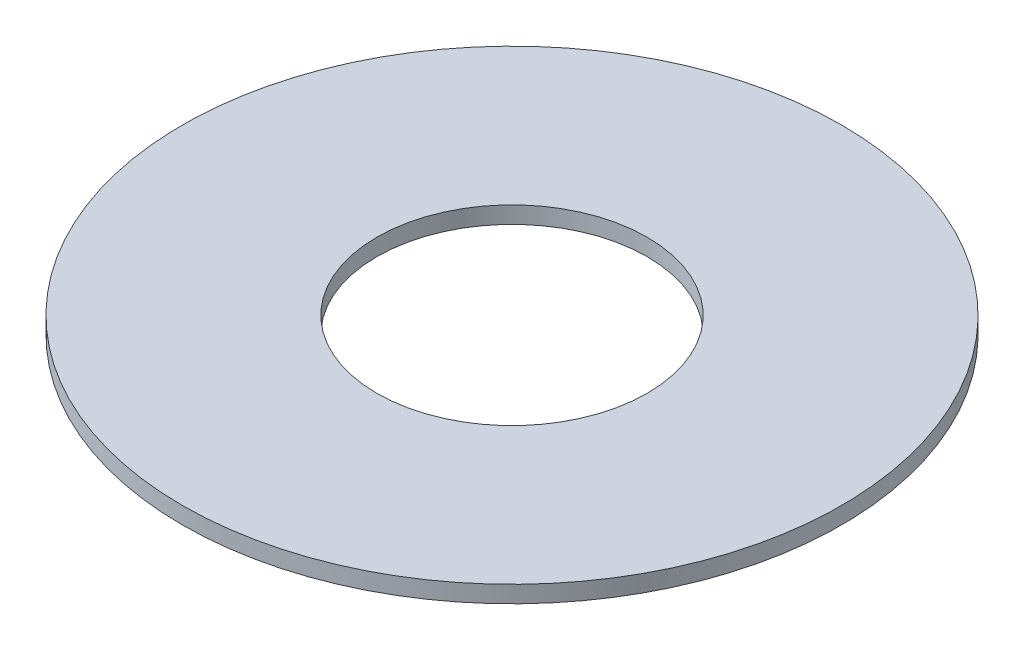
SolidWorks part; units mm, degrees
ref_plane "Front Plane" through (0, 0, 0) normal (0, 0, 1) x (1, 0, 0)
ref_plane "Top Plane" through (0, 0, 0) normal (0, 1, 0) x (1, 0, 0)
ref_plane "Right Plane" through (0, 0, 0) normal (1, 0, 0) x (0, 0, -1)
sketch "Sketch1" plane through (0, 0, 0) normal (0, 1, 0) x (1, 0, 0)
  circle A0 centre (0, 0) radius 97.5
  dimension "FLANGE_OD" = 195
extrude "Boss-Extrude1" add sketch "Sketch1" along normal blind 5
sketch "Sketch2" plane through (0, 0, 0) normal (0, 1, 0) x (1, 0, 0)
  circle A0 centre (0, 0) radius 40
  dimension "BORE_D" = 80
extrude "Cut-Extrude1" cut sketch "Sketch2" along normal through all
sketch "Sketch3" plane through (0, 5, 0) normal (0, 1, 0) x (1, 0, 0)
  circle A0 centre (0, 0) radius 32.1327 construction
  circle A1 centre (-32.1327, 0) radius 2.4227
  dimension "BOLT_D" = 4.8454
  dimension "BOLT_PCD" = 64.2654
extrude "Cut-Extrude2" cut sketch "Sketch3" against normal blind 4.9421 rebuild error yes
pattern_circular "CirPattern1" count 5 over 360 rebuild error yes
